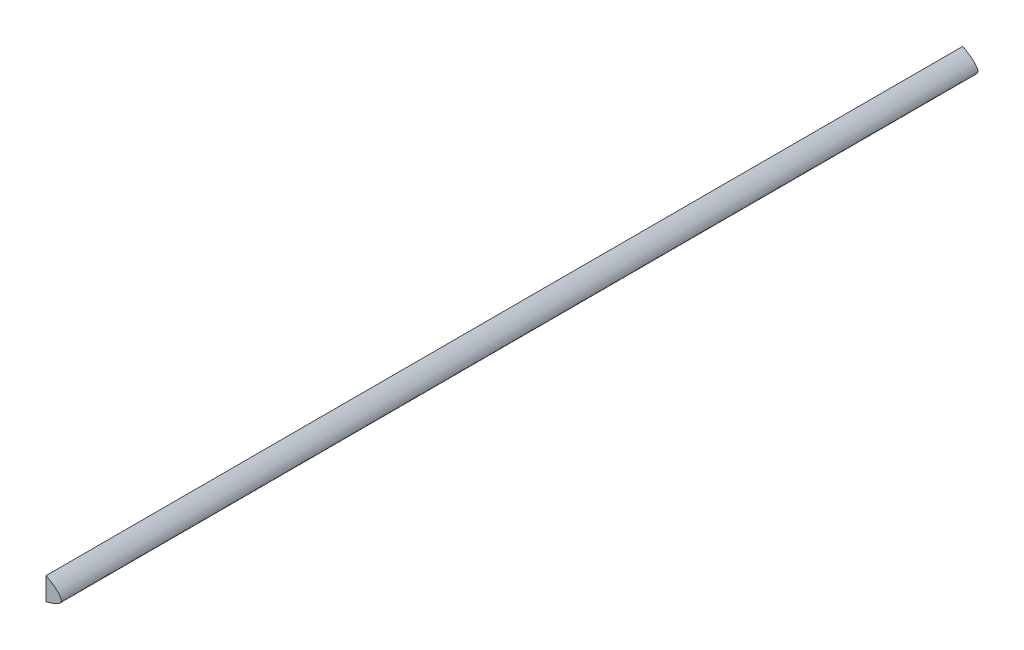
SolidWorks part; units mm, degrees
material "Balsa"
ref_plane "Front Plane" through (0, 0, 0) normal (0, 0, 1) x (1, 0, 0)
ref_plane "Top Plane" through (0, 0, 0) normal (0, 1, 0) x (1, 0, 0)
ref_plane "Right Plane" through (0, 0, 0) normal (1, 0, 0) x (0, 0, -1)
sketch "Sketch1" plane through (0, 0, 0) normal (0, 0, 1) x (1, 0, 0)
  line L0 (-12.7, 11.5883) -> (-12.7, -7.2627) construction
  line L1 (-12.7, 11.5883) -> (-12.7, -7.2627)
  line L3 (-12.7, -20.5931) -> (-357.6496, -20.5931)
  line L4 (-12.7, -20.5931) -> (-12.7, 32.1156)
  line L5 (-12.7, 32.1156) -> (-357.6496, 32.1156)
  line L6 (-357.6496, -20.5931) -> (-357.6496, 32.1156)
  spline S0 degree 3 poles (-354.9981, 0.2938) (-358.3317, -0.0432) (-354.9573, 0.0431) (-352.2525, -0.129) (-345.8395, -0.4061) (-338.1246, -0.9102) (-328.2104, -1.4385) (-316.6121, -2.0207) (-303.3148, -2.6922) (-288.5372, -3.4753) (-272.4652, -4.367) (-255.3201, -5.3536) (-237.3263, -6.4253) (-218.721, -7.5525) (-199.7442, -8.7119) (-180.6424, -9.8572) (-161.6617, -10.9405) (-143.0256, -11.8868) (-124.9052, -12.5651) (-107.4435, -12.9137) (-90.7897, -13.0132) (-75.1117, -12.8607) (-60.5842, -12.4624) (-47.3622, -11.8027) (-35.5828, -10.8813) (-25.3535, -9.7017) (-16.78, -8.2511) (-9.8754, -6.6365) (-4.805, -4.6528) (-1.2572, -2.9285) (0.4877, -0.018) (-1.1802, 2.9693) (-3.8158, 5.9031) (-8.1391, 9.1075) (-13.8914, 12.3237) (-21.1318, 15.5018) (-29.7714, 18.545) (-39.7523, 21.3791) (-50.9728, 23.9485) (-63.3272, 26.1868) (-76.6903, 28.0308) (-90.9433, 29.4155) (-105.9899, 30.2108) (-121.7437, 30.3922) (-138.1258, 29.947) (-155.0467, 28.9096) (-172.4086, 27.3328) (-190.087, 25.3152) (-207.9209, 23.0318) (-225.699, 20.6027) (-243.1815, 18.0913) (-260.1392, 15.5903) (-276.34, 13.1505) (-291.564, 10.8193) (-305.5952, 8.6507) (-318.2482, 6.6648) (-329.3081, 4.8919) (-338.7813, 3.2655) (-346.1763, 1.8676) (-352.3707, 0.8024) (-354.9981, 0.2938) (-358.3317, -0.0432) (-354.9573, 0.0431) knots -0.01488 -0.006827 -0.001748 0 0.001754 0.006889 0.015092 0.026071 0.039634 0.055674 0.074035 0.094459 0.116662 0.140359 0.165224 0.190938 0.217163 0.243564 0.269789 0.295501 0.320453 0.344504 0.367464 0.389075 0.409105 0.427344 0.443618 0.457786 0.469751 0.479454 0.486909 0.492196 0.495549 0.499383 0.50491 0.512186 0.521248 0.532096 0.5447 0.558973 0.574823 0.592114 0.610692 0.630393 0.651103 0.672759 0.695294 0.718616 0.742601 0.767121 0.79193 0.816685 0.841056 0.864707 0.887315 0.908565 0.928166 0.945829 0.961306 0.974428 0.98512 0.993173 0.998252 1 1.001754 1.006889 1.015092 only from (-357.6496, 0) to (-357.6496, 0) construction
  spline S1 degree 3 poles (-354.9981, 0.2938) (-358.3317, -0.0432) (-354.9573, 0.0431) (-352.2525, -0.129) (-345.8395, -0.4061) (-338.1246, -0.9102) (-328.2104, -1.4385) (-316.6121, -2.0207) (-303.3148, -2.6922) (-288.5372, -3.4753) (-272.4652, -4.367) (-255.3201, -5.3536) (-237.3263, -6.4253) (-218.721, -7.5525) (-199.7442, -8.7119) (-180.6424, -9.8572) (-161.6617, -10.9405) (-143.0256, -11.8868) (-124.9052, -12.5651) (-107.4435, -12.9137) (-90.7897, -13.0132) (-75.1117, -12.8607) (-60.5842, -12.4624) (-47.3622, -11.8027) (-35.5828, -10.8813) (-25.3535, -9.7017) (-16.78, -8.2511) (-9.8754, -6.6365) (-4.805, -4.6528) (-1.2572, -2.9285) (0.4877, -0.018) (-1.1802, 2.9693) (-3.8158, 5.9031) (-8.1391, 9.1075) (-13.8914, 12.3237) (-21.1318, 15.5018) (-29.7714, 18.545) (-39.7523, 21.3791) (-50.9728, 23.9485) (-63.3272, 26.1868) (-76.6903, 28.0308) (-90.9433, 29.4155) (-105.9899, 30.2108) (-121.7437, 30.3922) (-138.1258, 29.947) (-155.0467, 28.9096) (-172.4086, 27.3328) (-190.087, 25.3152) (-207.9209, 23.0318) (-225.699, 20.6027) (-243.1815, 18.0913) (-260.1392, 15.5903) (-276.34, 13.1505) (-291.564, 10.8193) (-305.5952, 8.6507) (-318.2482, 6.6648) (-329.3081, 4.8919) (-338.7813, 3.2655) (-346.1763, 1.8676) (-352.3707, 0.8024) (-354.9981, 0.2938) (-358.3317, -0.0432) (-354.9573, 0.0431) knots -0.01488 -0.006827 -0.001748 0 0.001754 0.006889 0.015092 0.026071 0.039634 0.055674 0.074035 0.094459 0.116662 0.140359 0.165224 0.190938 0.217163 0.243564 0.269789 0.295501 0.320453 0.344504 0.367464 0.389075 0.409105 0.427344 0.443618 0.457786 0.469751 0.479454 0.486909 0.492196 0.495549 0.499383 0.50491 0.512186 0.521248 0.532096 0.5447 0.558973 0.574823 0.592114 0.610692 0.630393 0.651103 0.672759 0.695294 0.718616 0.742601 0.767121 0.79193 0.816685 0.841056 0.864707 0.887315 0.908565 0.928166 0.945829 0.961306 0.974428 0.98512 0.993173 0.998252 1 1.001754 1.006889 1.015092 only from (-357.6496, 0) to (-357.6496, 0)
extrude "Boss-Extrude1" add sketch "Sketch1" against normal up to surface (761.9997 mm away) contours S1
extrude "Cut-Extrude1" cut sketch "Sketch1<3>" against normal up to surface (761.9997 mm away) contours S1 L1 region at (-148.7486, 7.0338, 0)
sketch "Sketch1<3>" plane through (0, 0, 0) normal (0, 0, 1) x (1, 0, 0) same geometry as "Sketch1"
